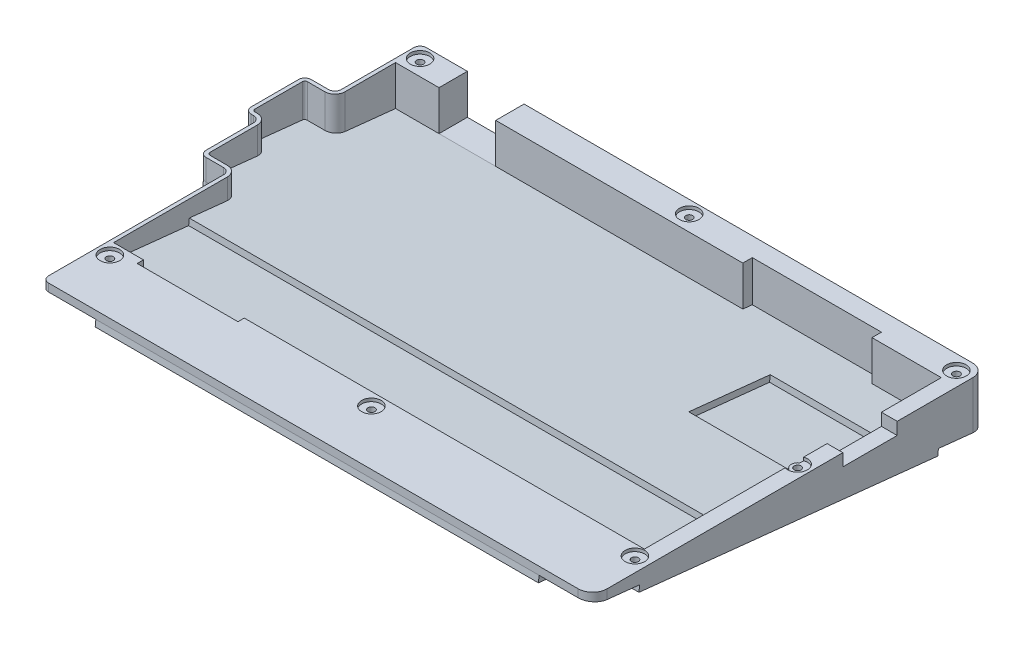
SolidWorks part; units mm, degrees
ref_plane "Front Plane" through (0, 0, 0) normal (0, 0, 1) x (1, 0, 0)
ref_plane "Top Plane" through (0, 0, 0) normal (0, 1, 0) x (1, 0, 0)
ref_plane "Right Plane" through (0, 0, 0) normal (1, 0, 0) x (0, 0, -1)
sketch "Sketch1" plane through (0, 0, 0) normal (0, 1, 0) x (1, 0, 0)
  line L0 (138.4196, 31.7518) -> (125.4196, 31.7518)
  line L1 (-35.0204, 31.7518) -> (107.4196, 31.7518)
  line L2 (140.4196, 29.7518) -> (140.4196, 6.7018)
  line L3 (-34.0204, 3.7518) -> (-34.0204, 22.7518)
  line L4 (136.4596, 27.7518) -> (136.4396, 27.7518)
  line L5 (142.4196, 4.7018) -> (147.9496, 4.7018)
  line L6 (-34.0204, 22.7518) -> (-12.0204, 22.7518)
  line L8 (149.9496, 2.7018) -> (149.9496, -12.3482)
  line L11 (147.9496, -14.3482) -> (147.1896, -14.3482)
  line L14 (145.1896, -16.3482) -> (145.1896, -31.3982)
  line L17 (143.1896, -33.3982) -> (137.6696, -33.3982)
  line L20 (135.6696, -35.3982) -> (135.6696, -77.4982)
  line L21 (-34.0204, -25.6003) -> (-34.0204, -71.4982)
  line L23 (133.6696, -79.4982) -> (-35.0204, -79.4982)
  line L28 (-39.0204, 27.7518) -> (-39.0204, 3.7518)
  line L31 (-34.0204, 3.7518) -> (-39.0204, 3.7518)
  line L32 (-34.0204, -13.4982) -> (-39.0204, -13.4982)
  line L33 (-39.0204, -75.4982) -> (-39.0204, -13.4982)
  line L34 (-34.0204, -71.4982) -> (92.9796, -71.4982)
  line L35 (92.9796, -71.4982) -> (92.9796, -73.4982)
  line L36 (92.9796, -73.4982) -> (124.9796, -73.4982)
  line L37 (124.9796, -73.4982) -> (124.9796, -71.4982)
  line L39 (134.4706, -35.3982) -> (134.4706, -71.4982)
  line L40 (134.4706, -71.4982) -> (124.9796, -71.4982)
  line L41 (137.6696, -32.1992) -> (143.1896, -32.1992)
  line L42 (-34.0204, -13.4982) -> (-34.0204, -22.1362)
  line L43 (143.9906, -31.3982) -> (143.9906, -16.3482)
  line L44 (-12.0204, 22.7518) -> (-12.0204, 25.7518)
  line L45 (147.1896, -13.1492) -> (147.9496, -13.1492)
  line L46 (148.7506, -12.3482) -> (148.7506, 2.7018)
  line L47 (-12.0204, 25.7518) -> (28.9796, 25.7518)
  line L48 (28.9796, 25.7518) -> (28.9796, 22.7518)
  line L49 (28.9796, 22.7518) -> (107.4196, 22.7518)
  line L50 (147.9496, 3.5027) -> (142.4196, 3.5027)
  line L51 (107.4196, 22.7518) -> (107.4196, 31.7518)
  line L52 (139.2206, 6.7018) -> (139.2206, 22.7518)
  line L53 (125.4196, 31.7518) -> (125.4196, 22.7518)
  line L54 (139.2206, 22.7518) -> (125.4196, 22.7518)
  arc A0 (138.4196, 31.7518) -> (140.4196, 29.7518) centre (138.4196, 29.7518) cw
  arc A1 (140.4196, 6.7018) -> (142.4196, 4.7018) centre (142.4196, 6.7018) ccw
  arc A2 (149.9496, 2.7018) -> (147.9496, 4.7018) centre (147.9496, 2.7018) ccw
  arc A3 (149.9496, -12.3482) -> (147.9496, -14.3482) centre (147.9496, -12.3482) cw
  arc A4 (147.1896, -14.3482) -> (145.1896, -16.3482) centre (147.1896, -16.3482) ccw
  arc A5 (145.1896, -31.3982) -> (143.1896, -33.3982) centre (143.1896, -31.3982) cw
  arc A6 (-35.0204, 31.7518) -> (-39.0204, 27.7518) centre (-35.0204, 27.7518) ccw
  arc A7 (-39.0204, -75.4982) -> (-35.0204, -79.4982) centre (-35.0204, -75.4982) ccw
  arc A8 (133.6696, -79.4982) -> (135.6696, -77.4982) centre (133.6696, -77.4982) ccw
  arc A9 (135.6696, -35.3982) -> (137.6696, -33.3982) centre (137.6696, -35.3982) cw
  circle A10 centre (-34.4204, 27.1518) radius 1.1
  circle A11 centre (51.0096, 27.7518) radius 1.1
  circle A12 centre (136.4396, 27.7518) radius 1.1
  circle A13 centre (-34.4204, -74.8982) radius 1.1
  circle A14 centre (48.6296, -75.4982) radius 1.1
  circle A15 centre (131.6496, -75.4982) radius 1.1
  circle A16 centre (-35.0204, -23.8682) radius 1.1
  arc A27 (-34.0204, -22.1362) -> (-34.0204, -25.6003) centre (-35.0204, -23.8682) cw
  arc A28 (139.2206, 6.7018) -> (142.4196, 3.5027) centre (142.4196, 6.7018) ccw
  arc A29 (147.9496, 3.5027) -> (148.7506, 2.7018) centre (147.9496, 2.7018) cw
  arc A30 (148.7506, -12.3482) -> (147.9496, -13.1492) centre (147.9496, -12.3482) cw
  arc A31 (147.1896, -13.1492) -> (143.9906, -16.3482) centre (147.1896, -16.3482) ccw
  arc A32 (143.9906, -31.3982) -> (143.1896, -32.1992) centre (143.1896, -31.3982) cw
  arc A33 (137.6696, -32.1992) -> (134.4706, -35.3982) centre (137.6696, -35.3982) ccw
extrude "Boss-Extrude2" add sketch "Sketch1" against normal blind 4.7 contours L41 A33 L39 L40 L37 L36 L35 L34 L21 A27 L42 L32 L33 A7 L23 A8 L20 A9 L17 A5 L14 A4 L11 A3 L8 A2 L5 A1 L2 A0 L0 L53 L54 L52 A28 L50 A29 L46 A30 L45 A31 L43 A32 A12 A13 A14 A15 | L1 A6 L28 L31 L3 L6 L44 L47 L48 L49 L51 A11 A10 region at (138.2833, 0, -29.6154) region at (31.7683, 0, -26.4895)
move or copy body "Body-Move/Copy1" bodies to move or copy 105 104 copy no rotation origin (55.4646, -2.35, 0) rotation axis (0, 0, 1) rotation angle 180
sketch "Sketch3" plane through (149.9496, 0, 0) normal (1, 0, 0) x (0, 0, -1)
  line L0 (-79.4982, 0) -> (-79.4982, -4.7) construction
  line L1 (-79.4982, 0) -> (-79.4982, -4.7)
  line L2 (31.7518, 0) -> (31.7518, -4.7) construction
  line L3 (31.7518, 0) -> (31.7518, -4.7)
  line L5 (-79.4982, -4.7) -> (31.7518, -16.3928)
  line L6 (31.7518, -16.3928) -> (31.7518, -4.7)
  line L7 (31.7518, -4.7) -> (-79.4982, -4.7)
  line M3 (-75.4982, -4.7) -> (-13.4982, -4.7)
  dimension "D1" = 6
extrude "Boss-Extrude3" add sketch "Sketch3" against normal up to surface (188.97 mm away) contours L6 L7 L5 M3 region at (149.9496, -8.5976, 5.3315) up to face at (-39.0204, -2.35, 4.8232)
sketch "Sketch4" plane through (0, -4.7, 0) normal (0, 1, 0) x (1, 0, 0)
  line L2 (145.9496, -79.4982) -> (149.9496, -79.4982)
  line L3 (149.9496, -79.4982) -> (149.9496, -75.4982)
  line L4 (-29.4904, 6.7018) -> (-29.4904, 29.7518)
  line L5 (-27.4904, 31.7518) -> (-39.0204, 31.7518)
  line L6 (-36.2604, -14.3482) -> (-37.0204, -14.3482)
  line L7 (-39.0204, -12.3482) -> (-39.0204, -79.4982)
  line L8 (-39.0204, -79.4982) -> (-22.7404, -79.4982)
  line L9 (-24.7404, -77.4982) -> (-24.7404, -35.3982)
  line L10 (-26.7404, -33.3982) -> (-32.2604, -33.3982)
  line L11 (-34.2604, -31.3982) -> (-34.2604, -16.3482)
  line L12 (-36.2604, -14.3482) -> (-37.0204, -14.3482)
  line L13 (-39.0204, -12.3482) -> (-39.0204, -79.4982)
  line L14 (-39.0204, -79.4982) -> (-22.7404, -79.4982)
  line L15 (-24.7404, -77.4982) -> (-24.7404, -35.3982)
  line L16 (-26.7404, -33.3982) -> (-32.2604, -33.3982)
  line L17 (-34.2604, -31.3982) -> (-34.2604, -16.3482)
  line L18 (-39.0204, 31.7518) -> (-39.0204, 2.7018)
  line L19 (-37.0204, 4.7018) -> (-31.4904, 4.7018)
  line L20 (-29.4904, 6.7018) -> (-29.4904, 29.7518)
  line L21 (-27.4904, 31.7518) -> (-39.0204, 31.7518)
  line L22 (-39.0204, 31.7518) -> (-39.0204, 2.7018)
  line L23 (-37.0204, 4.7018) -> (-31.4904, 4.7018)
  line L24 (145.9496, -79.4982) -> (149.9496, -79.4982)
  line L25 (149.9496, -79.4982) -> (149.9496, -75.4982)
  line L26 (149.9496, 31.7518) -> (145.9496, 31.7518)
  line L27 (149.9496, 27.7518) -> (149.9496, 31.7518)
  line L28 (149.9496, 31.7518) -> (145.9496, 31.7518)
  line L29 (149.9496, 27.7518) -> (149.9496, 31.7518)
  arc A1 (145.9496, -79.4982) -> (149.9496, -75.4982) centre (145.9496, -75.4982) ccw
  arc A2 (145.9496, -79.4982) -> (149.9496, -75.4982) centre (145.9496, -75.4982) ccw
  arc A3 (-27.4904, 31.7518) -> (-29.4904, 29.7518) centre (-27.4904, 29.7518) ccw
  arc A4 (-37.0204, 4.7018) -> (-39.0204, 2.7018) centre (-37.0204, 2.7018) ccw
  arc A5 (-39.0204, -12.3482) -> (-37.0204, -14.3482) centre (-37.0204, -12.3482) ccw
  arc A6 (-24.7404, -77.4982) -> (-22.7404, -79.4982) centre (-22.7404, -77.4982) ccw
  arc A7 (-24.7404, -35.3982) -> (-26.7404, -33.3982) centre (-26.7404, -35.3982) ccw
  arc A8 (-34.2604, -31.3982) -> (-32.2604, -33.3982) centre (-32.2604, -31.3982) ccw
  arc A9 (-34.2604, -16.3482) -> (-36.2604, -14.3482) centre (-36.2604, -16.3482) ccw
  arc A10 (-39.0204, -12.3482) -> (-37.0204, -14.3482) centre (-37.0204, -12.3482) ccw
  arc A11 (-24.7404, -77.4982) -> (-22.7404, -79.4982) centre (-22.7404, -77.4982) ccw
  arc A12 (-24.7404, -35.3982) -> (-26.7404, -33.3982) centre (-26.7404, -35.3982) ccw
  arc A13 (-34.2604, -31.3982) -> (-32.2604, -33.3982) centre (-32.2604, -31.3982) ccw
  arc A14 (-34.2604, -16.3482) -> (-36.2604, -14.3482) centre (-36.2604, -16.3482) ccw
  arc A15 (-31.4904, 4.7018) -> (-29.4904, 6.7018) centre (-31.4904, 6.7018) ccw
  arc A16 (-27.4904, 31.7518) -> (-29.4904, 29.7518) centre (-27.4904, 29.7518) ccw
  arc A17 (-37.0204, 4.7018) -> (-39.0204, 2.7018) centre (-37.0204, 2.7018) ccw
  arc A18 (-31.4904, 4.7018) -> (-29.4904, 6.7018) centre (-31.4904, 6.7018) ccw
  arc A19 (149.9496, 27.7518) -> (145.9496, 31.7518) centre (145.9496, 27.7518) ccw
  arc A20 (149.9496, 27.7518) -> (145.9496, 31.7518) centre (145.9496, 27.7518) ccw
  dimension "D1" = 0
  dimension "D2" = 0
  dimension "D3" = 0
  dimension "D4" = 0
extrude "Cut-Extrude1" cut sketch "Sketch4" against normal through all
ref_plane "Plane4" through (0, 15, 0) normal (0, 1, 0) x (1, 0, 0)
sketch "Sketch10" plane through (0, 15, 0) normal (0, 1, 0) x (1, 0, 0)
  line L0 (-14.4904, 22.7518) -> (3.5096, 22.7518)
  line L1 (144.9496, 3.7518) -> (144.9496, -13.4982)
  line L27 (-14.4904, 31.7518) -> (-14.4904, 22.7518)
  line L28 (-14.4904, 22.7518) -> (-28.2913, 22.7518)
  line L29 (-28.2913, 22.7518) -> (-28.2913, 6.7018)
  line L30 (-31.4904, 3.5027) -> (-37.0204, 3.5027)
  line L31 (-37.8213, 2.7018) -> (-37.8213, -12.3482)
  line L32 (-37.0204, -13.1492) -> (-36.2604, -13.1492)
  line L33 (-33.0613, -16.3482) -> (-33.0613, -31.3982)
  line L34 (-32.2604, -32.1992) -> (-26.7404, -32.1992)
  line L35 (-23.5413, -35.3982) -> (-23.5413, -71.4982)
  line L36 (-23.5413, -71.4982) -> (-14.0504, -71.4982)
  line L37 (-14.0504, -71.4982) -> (-14.0504, -73.4982)
  line L38 (-14.0504, -73.4982) -> (17.9496, -73.4982)
  line L39 (17.9496, -73.4982) -> (17.9496, -71.4982)
  line L40 (17.9496, -71.4982) -> (144.9496, -71.4982)
  line L41 (144.9496, -71.4982) -> (144.9496, -25.6003)
  line L42 (144.9496, -22.1362) -> (144.9496, -13.4982)
  line L43 (144.9496, -13.4982) -> (149.9496, -13.4982)
  line L44 (149.9496, -13.4982) -> (149.9496, 3.7518)
  line L45 (149.9496, 3.7518) -> (144.9496, 3.7518)
  line L46 (144.9496, 3.7518) -> (144.9496, 22.7518)
  line L47 (144.9496, 22.7518) -> (122.9496, 22.7518)
  line L48 (122.9496, 22.7518) -> (122.9496, 25.7518)
  line L49 (122.9496, 25.7518) -> (81.9496, 25.7518)
  line L50 (81.9496, 25.7518) -> (81.9496, 22.7518)
  line L51 (81.9496, 22.7518) -> (3.5096, 22.7518)
  line L52 (3.5096, 22.7518) -> (3.5096, 31.7518)
  line L53 (3.5096, 31.7518) -> (-14.4904, 31.7518)
  line L54 (-14.4904, 31.7518) -> (-14.4904, 22.7518)
  line L55 (-14.4904, 22.7518) -> (-28.2913, 22.7518)
  line L56 (-28.2913, 22.7518) -> (-28.2913, 6.7018)
  line L57 (-31.4904, 3.5027) -> (-37.0204, 3.5027)
  line L58 (-37.8213, 2.7018) -> (-37.8213, -12.3482)
  line L59 (-37.0204, -13.1492) -> (-36.2604, -13.1492)
  line L60 (-33.0613, -16.3482) -> (-33.0613, -31.3982)
  line L61 (-32.2604, -32.1992) -> (-26.7404, -32.1992)
  line L62 (-23.5413, -35.3982) -> (-23.5413, -71.4982)
  line L63 (-23.5413, -71.4982) -> (-14.0504, -71.4982)
  line L64 (-14.0504, -71.4982) -> (-14.0504, -73.4982)
  line L65 (-14.0504, -73.4982) -> (17.9496, -73.4982)
  line L66 (17.9496, -73.4982) -> (17.9496, -71.4982)
  line L67 (17.9496, -71.4982) -> (144.9496, -71.4982)
  line L68 (144.9496, -71.4982) -> (144.9496, -25.6003)
  line L69 (144.9496, -22.1362) -> (144.9496, -13.4982)
  line L70 (144.9496, -13.4982) -> (149.9496, -13.4982)
  line L71 (149.9496, -13.4982) -> (149.9496, 3.7518)
  line L72 (149.9496, 3.7518) -> (144.9496, 3.7518)
  line L73 (144.9496, 3.7518) -> (144.9496, 22.7518)
  line L74 (144.9496, 22.7518) -> (122.9496, 22.7518)
  line L75 (122.9496, 22.7518) -> (122.9496, 25.7518)
  line L76 (122.9496, 25.7518) -> (81.9496, 25.7518)
  line L77 (81.9496, 25.7518) -> (81.9496, 22.7518)
  line L78 (81.9496, 22.7518) -> (3.5096, 22.7518)
  line L79 (3.5096, 22.7518) -> (3.5096, 31.7518)
  line L80 (3.5096, 31.7518) -> (-14.4904, 31.7518)
  arc A7 (-31.4904, 3.5027) -> (-28.2913, 6.7018) centre (-31.4904, 6.7018) ccw
  arc A8 (-37.0204, 3.5027) -> (-37.8213, 2.7018) centre (-37.0204, 2.7018) ccw
  arc A9 (-37.8213, -12.3482) -> (-37.0204, -13.1492) centre (-37.0204, -12.3482) ccw
  arc A10 (-33.0613, -16.3482) -> (-36.2604, -13.1492) centre (-36.2604, -16.3482) ccw
  arc A11 (-33.0613, -31.3982) -> (-32.2604, -32.1992) centre (-32.2604, -31.3982) ccw
  arc A12 (-23.5413, -35.3982) -> (-26.7404, -32.1992) centre (-26.7404, -35.3982) ccw
  arc A13 (144.9496, -22.1362) -> (144.9496, -25.6003) centre (145.9496, -23.8682) ccw
  arc A14 (-31.4904, 3.5027) -> (-28.2913, 6.7018) centre (-31.4904, 6.7018) ccw
  arc A15 (-37.0204, 3.5027) -> (-37.8213, 2.7018) centre (-37.0204, 2.7018) ccw
  arc A16 (-37.8213, -12.3482) -> (-37.0204, -13.1492) centre (-37.0204, -12.3482) ccw
  arc A17 (-33.0613, -16.3482) -> (-36.2604, -13.1492) centre (-36.2604, -16.3482) ccw
  arc A18 (-33.0613, -31.3982) -> (-32.2604, -32.1992) centre (-32.2604, -31.3982) ccw
  arc A19 (-23.5413, -35.3982) -> (-26.7404, -32.1992) centre (-26.7404, -35.3982) ccw
  arc A20 (144.9496, -22.1362) -> (144.9496, -25.6003) centre (145.9496, -23.8682) ccw
  dimension "D1" = 0
extrude "Cut-Extrude2" cut sketch "Sketch10" against normal through all contours A20 L69 L1 L73 L74 L75 L76 L77 L78 L0 L55 L56 A14 L57 A15 L58 A16 L59 A17 L60 A18 L61 A19 L62 L63 L64 L65 L66 L67 L68 region at (57.9798, 15, 23.6888)
sketch "Sketch11" plane through (144.9496, 0, 0) normal (-1, 0, 0) x (0, 0, 1)
  line L0 (-22.7518, -15.4469) -> (71.4982, -5.5408)
  line L1 (71.4982, -5.5408) -> (71.4982, -3.5408)
  line L2 (71.4982, 0) -> (71.4982, -5.5408) construction
  line L3 (71.4982, -3.5408) -> (-22.7518, -13.4469)
  line L4 (-22.7518, 0) -> (-22.7518, -15.4469) construction
  line L5 (-22.7518, -13.4469) -> (-22.7518, -15.4469)
  dimension "D1" = 2
  dimension "D2" = 2
extrude "Boss-Extrude4" add sketch "Sketch11" along normal up to surface (182.7709 mm away)
sketch "Sketch12" plane through (0, -10.9348, 1.1493) normal (0, 0.9945, -0.1045) x (1, 0, 0)
  line L0 (-29.4904, 7.8943) -> (-29.4904, 24.0327) construction
  line L1 (-29.4904, 24.0327) -> (-37.8213, 24.0327) construction
  line L2 (-37.8213, 24.0327) -> (-37.8213, 5.715) construction
  line L3 (-37.0204, 5.8833) -> (-31.4904, 5.8833) construction
  line L4 (-36.2604, -13.2716) -> (-37.0204, -13.2716) construction
  line L5 (-37.8213, -13.1033) -> (-37.8213, -70.7364) construction
  line L6 (-37.8213, -70.7364) -> (-24.7404, -70.7364) construction
  line L7 (-24.7404, -70.7364) -> (-24.7404, -34.4376) construction
  line L8 (-26.7404, -32.4266) -> (-32.2604, -32.4266) construction
  line L9 (-34.2604, -30.4155) -> (-34.2604, -15.2826) construction
  line L10 (-29.4904, 7.8943) -> (-29.4904, 24.0327)
  line L11 (-29.4904, 24.0327) -> (-37.8213, 24.0327)
  line L12 (-37.8213, 24.0327) -> (-37.8213, 5.715)
  line L13 (-37.0204, 5.8833) -> (-31.4904, 5.8833)
  line L14 (-36.2604, -13.2716) -> (-37.0204, -13.2716)
  line L15 (-37.8213, -13.1033) -> (-37.8213, -70.7364)
  line L16 (-37.8213, -70.7364) -> (-24.7404, -70.7364)
  line L17 (-24.7404, -70.7364) -> (-24.7404, -34.4376)
  line L18 (-26.7404, -32.4266) -> (-32.2604, -32.4266)
  line L19 (-34.2604, -30.4155) -> (-34.2604, -15.2826)
  line L20 (-37.8213, 24.0327) -> (-37.8213, 25.9101)
  line L21 (-29.4904, 24.0327) -> (-29.4904, 27.1127)
  line L22 (-29.4904, 27.1127) -> (-37.8213, 25.9101)
  ellipse E0 centre (-31.4904, 7.8943) end of major axis (-31.4904, 9.9053) minor radius 2 (-31.4904, 5.8833) -> (-29.4904, 7.8943) ccw construction
  ellipse E1 centre (-37.0204, 3.8723) end of major axis (-37.0204, 5.8833) minor radius 2 (-37.0204, 5.8833) -> (-37.8213, 5.715) ccw construction
  ellipse E2 centre (-37.0204, -11.2606) end of major axis (-37.0204, -9.2496) minor radius 2 (-37.8213, -13.1033) -> (-37.0204, -13.2716) ccw construction
  ellipse E3 centre (-26.7404, -34.4376) end of major axis (-26.7404, -32.4266) minor radius 2 (-24.7404, -34.4376) -> (-26.7404, -32.4266) ccw construction
  ellipse E4 centre (-32.2604, -30.4155) end of major axis (-32.2604, -28.4045) minor radius 2 (-34.2604, -30.4155) -> (-32.2604, -32.4266) ccw construction
  ellipse E5 centre (-36.2604, -15.2826) end of major axis (-36.2604, -13.2716) minor radius 2 (-34.2604, -15.2826) -> (-36.2604, -13.2716) ccw construction
  ellipse E6 centre (-31.4904, 7.8943) end of major axis (-31.4904, 9.9053) minor radius 2 (-31.4904, 5.8833) -> (-29.4904, 7.8943) ccw
  ellipse E7 centre (-37.0204, 3.8723) end of major axis (-37.0204, 5.8833) minor radius 2 (-37.0204, 5.8833) -> (-37.8213, 5.715) ccw
  ellipse E8 centre (-37.0204, -11.2606) end of major axis (-37.0204, -9.2496) minor radius 2 (-37.8213, -13.1033) -> (-37.0204, -13.2716) ccw
  ellipse E9 centre (-26.7404, -34.4376) end of major axis (-26.7404, -32.4266) minor radius 2 (-24.7404, -34.4376) -> (-26.7404, -32.4266) ccw
  ellipse E10 centre (-32.2604, -30.4155) end of major axis (-32.2604, -28.4045) minor radius 2 (-34.2604, -30.4155) -> (-32.2604, -32.4266) ccw
  ellipse E11 centre (-36.2604, -15.2826) end of major axis (-36.2604, -13.2716) minor radius 2 (-34.2604, -15.2826) -> (-36.2604, -13.2716) ccw
sketch "Sketch26" plane through (-37.8213, 0, 0) normal (-1, 0, 0) x (0, 0, 1)
  line L0 (14.1808, -9.5651) -> (-4.5344, -11.5322)
  line L1 (-4.5344, -13.5322) -> (14.1808, -11.5651)
  line L4 (-22.7518, -15.4469) -> (-4.5344, -13.5322)
  line L5 (-4.5344, -13.5322) -> (-4.5344, -11.5322)
  line L6 (-4.5344, -11.5322) -> (-22.7518, -13.4469)
  line L7 (-22.7518, -13.4469) -> (-22.7518, -15.4469)
  line L8 (-22.7518, -15.4469) -> (-4.5344, -13.5322)
  line L9 (-4.5344, -13.5322) -> (-4.5344, -11.5322)
  line L10 (-4.5344, -11.5322) -> (-22.7518, -13.4469)
  line L11 (-22.7518, -13.4469) -> (-22.7518, -15.4469)
  line L12 (14.1808, -9.5651) -> (14.1808, -11.5651)
  line L13 (14.1808, -11.5651) -> (71.4982, -5.5408)
  line L14 (71.4982, -5.5408) -> (71.4982, -3.5408)
  line L15 (71.4982, -3.5408) -> (14.1808, -9.5651)
  line L16 (14.1808, -9.5651) -> (14.1808, -11.5651)
  line L17 (14.1808, -11.5651) -> (71.4982, -5.5408)
  line L18 (71.4982, -5.5408) -> (71.4982, -3.5408)
  line L19 (71.4982, -3.5408) -> (14.1808, -9.5651)
  line M9 (14.1808, -9.5651) -> (14.1808, -11.5651)
  line M10 (14.1808, -11.5651) -> (71.4982, -5.5408)
  line M11 (71.4982, -5.5408) -> (71.4982, -3.5408)
  line M12 (71.4982, -3.5408) -> (14.1808, -9.5651)
  dimension "D1" = 0
  dimension "D2" = 0
extrude "Boss-Extrude10" add sketch "Sketch26" along normal blind 11 contours L10 L11 L8 L9 | L9 L1 L0 M9 | M12 M9 M10 M11 region at (-37.8213, -11.5487, 4.8232) region at (-37.8213, -7.553, 42.8395) region at (-37.8213, -13.4895, -13.6431)
sketch "Sketch28" plane through (0, -10.9348, 1.1493) normal (0, 0.9945, -0.1045) x (1, 0, 0)
  line L0 (-48.8213, 24.0327) -> (-52.7132, 28.3929)
  line L1 (-52.7132, 28.3929) -> (-29.4904, 30.8021)
  line L2 (-29.4904, 30.8021) -> (-29.4904, 24.0327)
  line L10 (-29.4904, 7.8943) -> (-29.4904, 24.0327)
  line L11 (-29.4904, 24.0327) -> (-48.8213, 24.0327)
  line L12 (-48.8213, 24.0327) -> (-48.8213, -70.7364)
  line L13 (-48.8213, -70.7364) -> (-24.7404, -70.7364)
  line L14 (-24.7404, -70.7364) -> (-24.7404, -34.4376)
  line L15 (-26.7404, -32.4266) -> (-32.2604, -32.4266)
  line L16 (-34.2604, -30.4155) -> (-34.2604, -15.2826)
  line L17 (-36.2604, -13.2716) -> (-37.0204, -13.2716)
  line L18 (-39.0204, -11.2606) -> (-39.0204, 3.8723)
  line L19 (-37.0204, 5.8833) -> (-31.4904, 5.8833)
  line L20 (-29.4904, 7.8943) -> (-29.4904, 24.0327)
  line L21 (-29.4904, 24.0327) -> (-48.8213, 24.0327)
  line L22 (-48.8213, 24.0327) -> (-48.8213, -70.7364)
  line L23 (-48.8213, -70.7364) -> (-24.7404, -70.7364)
  line L24 (-24.7404, -70.7364) -> (-24.7404, -34.4376)
  line L25 (-26.7404, -32.4266) -> (-32.2604, -32.4266)
  line L26 (-34.2604, -30.4155) -> (-34.2604, -15.2826)
  line L27 (-36.2604, -13.2716) -> (-37.0204, -13.2716)
  line L28 (-39.0204, -11.2606) -> (-39.0204, 3.8723)
  line L29 (-37.0204, 5.8833) -> (-31.4904, 5.8833)
  ellipse E6 centre (-31.4904, 7.8943) end of major axis (-31.4904, 9.9053) minor radius 2 (-31.4904, 5.8833) -> (-29.4904, 7.8943) ccw
  ellipse E7 centre (-26.7404, -34.4376) end of major axis (-26.7404, -32.4266) minor radius 2 (-24.7404, -34.4376) -> (-26.7404, -32.4266) ccw
  ellipse E8 centre (-32.2604, -30.4155) end of major axis (-32.2604, -28.4045) minor radius 2 (-34.2604, -30.4155) -> (-32.2604, -32.4266) ccw
  ellipse E9 centre (-36.2604, -15.2826) end of major axis (-36.2604, -13.2716) minor radius 2 (-34.2604, -15.2826) -> (-36.2604, -13.2716) ccw
  ellipse E10 centre (-37.0204, -11.2606) end of major axis (-37.0204, -9.2496) minor radius 2 (-39.0204, -11.2606) -> (-37.0204, -13.2716) ccw
  ellipse E11 centre (-37.0204, 3.8723) end of major axis (-37.0204, 5.8833) minor radius 2 (-37.0204, 5.8833) -> (-39.0204, 3.8723) ccw
  ellipse E12 centre (-31.4904, 7.8943) end of major axis (-31.4904, 9.9053) minor radius 2 (-31.4904, 5.8833) -> (-29.4904, 7.8943) ccw
  ellipse E13 centre (-26.7404, -34.4376) end of major axis (-26.7404, -32.4266) minor radius 2 (-24.7404, -34.4376) -> (-26.7404, -32.4266) ccw
  ellipse E14 centre (-32.2604, -30.4155) end of major axis (-32.2604, -28.4045) minor radius 2 (-34.2604, -30.4155) -> (-32.2604, -32.4266) ccw
  ellipse E15 centre (-36.2604, -15.2826) end of major axis (-36.2604, -13.2716) minor radius 2 (-34.2604, -15.2826) -> (-36.2604, -13.2716) ccw
  ellipse E16 centre (-37.0204, -11.2606) end of major axis (-37.0204, -9.2496) minor radius 2 (-39.0204, -11.2606) -> (-37.0204, -13.2716) ccw
  ellipse E17 centre (-37.0204, 3.8723) end of major axis (-37.0204, 5.8833) minor radius 2 (-37.0204, 5.8833) -> (-39.0204, 3.8723) ccw
  ellipse M17 centre (-31.4904, 7.8943) end of major axis (-31.4904, 9.9053) minor radius 2 (-31.4904, 5.8833) -> (-29.4904, 7.8943) ccw
  line M18 (-29.4904, 7.8943) -> (-29.4904, 24.0327)
  line M19 (-29.4904, 24.0327) -> (-48.8213, 24.0327)
  line M20 (-48.8213, 24.0327) -> (-48.8213, -70.7364)
  line M21 (-48.8213, -70.7364) -> (-24.7404, -70.7364)
  line M22 (-24.7404, -70.7364) -> (-24.7404, -34.4376)
  ellipse M23 centre (-26.7404, -34.4376) end of major axis (-26.7404, -32.4266) minor radius 2 (-24.7404, -34.4376) -> (-26.7404, -32.4266) ccw
  line M24 (-26.7404, -32.4266) -> (-32.2604, -32.4266)
  ellipse M25 centre (-32.2604, -30.4155) end of major axis (-32.2604, -28.4045) minor radius 2 (-32.2604, -32.4266) -> (-34.2604, -30.4155) cw
  line M26 (-34.2604, -30.4155) -> (-34.2604, -15.2826)
  ellipse M27 centre (-36.2604, -15.2826) end of major axis (-36.2604, -13.2716) minor radius 2 (-34.2604, -15.2826) -> (-36.2604, -13.2716) ccw
  line M28 (-36.2604, -13.2716) -> (-37.0204, -13.2716)
  ellipse M29 centre (-37.0204, -11.2606) end of major axis (-37.0204, -9.2496) minor radius 2 (-37.0204, -13.2716) -> (-39.0204, -11.2606) cw
  line M30 (-39.0204, -11.2606) -> (-39.0204, 3.8723)
  ellipse M31 centre (-37.0204, 3.8723) end of major axis (-37.0204, 5.8833) minor radius 2 (-39.0204, 3.8723) -> (-37.0204, 5.8833) cw
  line M32 (-37.0204, 5.8833) -> (-31.4904, 5.8833)
  dimension "D1" = 0
extrude "Cut-Extrude8" cut sketch "Sketch28" against normal blind 11 contours M32 M17 M18 M19 M20 M21 M22 M23 M24 M25 M26 M27 M28 M29 M30 M31 | L2 L1 L0 M19 region at (-39.4803, -13.7524, -25.6581) region at (-38.8035, -7.967, 29.3861)
sketch "Sketch30" plane through (122.9496, 0, 0) normal (-1, 0, 0) x (0, 0, 1)
  line L0 (-25.7518, -15.7622) -> (-22.7518, -15.4469)
  line L1 (-22.7518, -15.4469) -> (-22.7518, -13.4469)
  line L2 (-22.7518, -15.4469) -> (-22.7518, -13.4469) construction
  line L3 (-22.7518, -13.4469) -> (-25.7518, -13.7622)
  line L4 (-25.7518, 0) -> (-25.7518, -15.7622) construction
  line L5 (-25.7518, -13.7622) -> (-25.7518, -15.7622)
extrude "Boss-Extrude11" add sketch "Sketch30" along normal up to surface (41 mm away)
sketch "Sketch32" plane through (17.9496, 0, 0) normal (-1, 0, 0) x (0, 0, 1)
  line L0 (73.4982, -5.3306) -> (71.4982, -5.5408)
  line L1 (71.4982, -5.5408) -> (71.4982, -3.5408)
  line L2 (71.4982, -3.5408) -> (73.4982, -3.3306)
  line L3 (73.4982, 0) -> (73.4982, -5.3306) construction
  line L4 (73.4982, -3.3306) -> (73.4982, -5.3306)
  dimension "D1" = 2
extrude "Boss-Extrude14" add sketch "Sketch32" along normal up to surface (32 mm away)
sketch "Sketch35" plane through (0, 0, 0) normal (0, 1, 0) x (1, 0, 0)
  line L0 (149.9496, 3.7518) -> (149.9496, -13.4982)
  line L1 (149.9496, -13.4982) -> (144.9496, -13.4982)
  line L2 (144.9496, -13.4982) -> (144.9496, 3.7518)
  line L3 (144.9496, 3.7518) -> (149.9496, 3.7518)
ref_plane "Plane5" through (149.9496, -5.1204, 75.4982) normal (0, -1, 0) x (-1, 0, 0)
sketch "Sketch47" plane through (0, 0, 0) normal (0, 1, 0) x (1, 0, 0)
  circle A0 centre (145.3496, -74.8982) radius 3.1
  circle A1 centre (62.2996, -75.4982) radius 3.1
  circle A2 centre (-20.7204, -75.4982) radius 3.1
  circle A3 centre (-25.5104, 27.7518) radius 3.1
  circle A4 centre (59.9196, 27.7518) radius 3.1
  circle A5 centre (145.3496, 27.1518) radius 3.1
  circle A6 centre (145.9496, -23.8682) radius 3.1
extrude "Cut-Extrude17" cut sketch "Sketch47" against normal blind 1.8
sketch "Sketch48" plane through (0, 0, 0) normal (0, 1, 0) x (1, 0, 0)
  line L10 (145.9496, 31.7518) -> (3.5096, 31.7518)
  line L11 (3.5096, 31.7518) -> (3.5096, 22.7518)
  line L12 (3.5096, 22.7518) -> (81.9496, 22.7518)
  line L13 (81.9496, 22.7518) -> (81.9496, 25.7518)
  line L14 (81.9496, 25.7518) -> (122.9496, 25.7518)
  line L15 (122.9496, 25.7518) -> (122.9496, 22.7518)
  line L16 (122.9496, 22.7518) -> (144.9496, 22.7518)
  line L17 (144.9496, 22.7518) -> (144.9496, 3.7518)
  line L18 (144.9496, 3.7518) -> (149.9496, 3.7518)
  line L19 (149.9496, 3.7518) -> (149.9496, 27.7518)
  line L20 (145.9496, 31.7518) -> (3.5096, 31.7518)
  line L21 (3.5096, 31.7518) -> (3.5096, 22.7518)
  line L22 (3.5096, 22.7518) -> (81.9496, 22.7518)
  line L23 (81.9496, 22.7518) -> (81.9496, 25.7518)
  line L24 (81.9496, 25.7518) -> (122.9496, 25.7518)
  line L25 (122.9496, 25.7518) -> (122.9496, 22.7518)
  line L26 (122.9496, 22.7518) -> (144.9496, 22.7518)
  line L27 (144.9496, 22.7518) -> (144.9496, 3.7518)
  line L28 (144.9496, 3.7518) -> (149.9496, 3.7518)
  line L29 (149.9496, 3.7518) -> (149.9496, 27.7518)
  line L47 (144.9496, -13.4982) -> (144.9496, -20.9339)
  line L48 (144.9496, -26.8025) -> (144.9496, -71.4982)
  line L49 (144.9496, -71.4982) -> (17.9496, -71.4982)
  line L50 (17.9496, -71.4982) -> (17.9496, -73.4982)
  line L51 (17.9496, -73.4982) -> (-14.0504, -73.4982)
  line L52 (-14.0504, -73.4982) -> (-14.0504, -71.4982)
  line L53 (-14.0504, -71.4982) -> (-23.5413, -71.4982)
  line L54 (-23.5413, -71.4982) -> (-23.5413, -35.3982)
  line L55 (-26.7404, -32.1992) -> (-32.2604, -32.1992)
  line L56 (-33.0613, -31.3982) -> (-33.0613, -16.3482)
  line L57 (-36.2604, -13.1492) -> (-37.0204, -13.1492)
  line L58 (-37.8213, -12.3482) -> (-37.8213, 2.7018)
  line L59 (-37.0204, 3.5027) -> (-31.4904, 3.5027)
  line L60 (-28.2913, 6.7018) -> (-28.2913, 22.7518)
  line L61 (-28.2913, 22.7518) -> (-14.4904, 22.7518)
  line L62 (-14.4904, 22.7518) -> (-14.4904, 31.7518)
  line L63 (-14.4904, 31.7518) -> (-27.4904, 31.7518)
  line L64 (-29.4904, 29.7518) -> (-29.4904, 6.7018)
  line L65 (-31.4904, 4.7018) -> (-37.0204, 4.7018)
  line L66 (-39.0204, 2.7018) -> (-39.0204, -12.3482)
  line L67 (-37.0204, -14.3482) -> (-36.2604, -14.3482)
  line L68 (-34.2604, -16.3482) -> (-34.2604, -31.3982)
  line L69 (-32.2604, -33.3982) -> (-26.7404, -33.3982)
  line L70 (-24.7404, -35.3982) -> (-24.7404, -77.4982)
  line L71 (-22.7404, -79.4982) -> (145.9496, -79.4982)
  line L72 (149.9496, -75.4982) -> (149.9496, -13.4982)
  line L73 (149.9496, -13.4982) -> (144.9496, -13.4982)
  line L74 (144.9496, -13.4982) -> (144.9496, -20.9339)
  line L75 (144.9496, -26.8025) -> (144.9496, -71.4982)
  line L76 (144.9496, -71.4982) -> (17.9496, -71.4982)
  line L77 (17.9496, -71.4982) -> (17.9496, -73.4982)
  line L78 (17.9496, -73.4982) -> (-14.0504, -73.4982)
  line L79 (-14.0504, -73.4982) -> (-14.0504, -71.4982)
  line L80 (-14.0504, -71.4982) -> (-23.5413, -71.4982)
  line L81 (-23.5413, -71.4982) -> (-23.5413, -35.3982)
  line L82 (-26.7404, -32.1992) -> (-32.2604, -32.1992)
  line L83 (-33.0613, -31.3982) -> (-33.0613, -16.3482)
  line L84 (-36.2604, -13.1492) -> (-37.0204, -13.1492)
  line L85 (-37.8213, -12.3482) -> (-37.8213, 2.7018)
  line L86 (-37.0204, 3.5027) -> (-31.4904, 3.5027)
  line L87 (-28.2913, 6.7018) -> (-28.2913, 22.7518)
  line L88 (-28.2913, 22.7518) -> (-14.4904, 22.7518)
  line L89 (-14.4904, 22.7518) -> (-14.4904, 31.7518)
  line L90 (-14.4904, 31.7518) -> (-27.4904, 31.7518)
  line L91 (-29.4904, 29.7518) -> (-29.4904, 6.7018)
  line L92 (-31.4904, 4.7018) -> (-37.0204, 4.7018)
  line L93 (-39.0204, 2.7018) -> (-39.0204, -12.3482)
  line L94 (-37.0204, -14.3482) -> (-36.2604, -14.3482)
  line L95 (-34.2604, -16.3482) -> (-34.2604, -31.3982)
  line L96 (-32.2604, -33.3982) -> (-26.7404, -33.3982)
  line L97 (-24.7404, -35.3982) -> (-24.7404, -77.4982)
  line L98 (-22.7404, -79.4982) -> (145.9496, -79.4982)
  line L99 (149.9496, -75.4982) -> (149.9496, -13.4982)
  line L100 (149.9496, -13.4982) -> (144.9496, -13.4982)
  arc A1 (149.9496, 27.7518) -> (145.9496, 31.7518) centre (145.9496, 27.7518) ccw
  arc A2 (149.9496, 27.7518) -> (145.9496, 31.7518) centre (145.9496, 27.7518) ccw
  arc A18 (144.9496, -26.8025) -> (144.9496, -20.9339) centre (145.9496, -23.8682) ccw
  arc A19 (-23.5413, -35.3982) -> (-26.7404, -32.1992) centre (-26.7404, -35.3982) ccw
  arc A20 (-33.0613, -31.3982) -> (-32.2604, -32.1992) centre (-32.2604, -31.3982) ccw
  arc A21 (-33.0613, -16.3482) -> (-36.2604, -13.1492) centre (-36.2604, -16.3482) ccw
  arc A22 (-37.8213, -12.3482) -> (-37.0204, -13.1492) centre (-37.0204, -12.3482) ccw
  arc A23 (-37.0204, 3.5027) -> (-37.8213, 2.7018) centre (-37.0204, 2.7018) ccw
  arc A24 (-31.4904, 3.5027) -> (-28.2913, 6.7018) centre (-31.4904, 6.7018) ccw
  arc A25 (-27.4904, 31.7518) -> (-29.4904, 29.7518) centre (-27.4904, 29.7518) ccw
  arc A26 (-31.4904, 4.7018) -> (-29.4904, 6.7018) centre (-31.4904, 6.7018) ccw
  arc A27 (-37.0204, 4.7018) -> (-39.0204, 2.7018) centre (-37.0204, 2.7018) ccw
  arc A28 (-39.0204, -12.3482) -> (-37.0204, -14.3482) centre (-37.0204, -12.3482) ccw
  arc A29 (-34.2604, -16.3482) -> (-36.2604, -14.3482) centre (-36.2604, -16.3482) ccw
  arc A30 (-34.2604, -31.3982) -> (-32.2604, -33.3982) centre (-32.2604, -31.3982) ccw
  arc A31 (-24.7404, -35.3982) -> (-26.7404, -33.3982) centre (-26.7404, -35.3982) ccw
  arc A32 (-24.7404, -77.4982) -> (-22.7404, -79.4982) centre (-22.7404, -77.4982) ccw
  arc A33 (145.9496, -79.4982) -> (149.9496, -75.4982) centre (145.9496, -75.4982) ccw
  arc A34 (144.9496, -26.8025) -> (144.9496, -20.9339) centre (145.9496, -23.8682) ccw
  arc A35 (-23.5413, -35.3982) -> (-26.7404, -32.1992) centre (-26.7404, -35.3982) ccw
  arc A36 (-33.0613, -31.3982) -> (-32.2604, -32.1992) centre (-32.2604, -31.3982) ccw
  arc A37 (-33.0613, -16.3482) -> (-36.2604, -13.1492) centre (-36.2604, -16.3482) ccw
  arc A38 (-37.8213, -12.3482) -> (-37.0204, -13.1492) centre (-37.0204, -12.3482) ccw
  arc A39 (-37.0204, 3.5027) -> (-37.8213, 2.7018) centre (-37.0204, 2.7018) ccw
  arc A40 (-31.4904, 3.5027) -> (-28.2913, 6.7018) centre (-31.4904, 6.7018) ccw
  arc A41 (-27.4904, 31.7518) -> (-29.4904, 29.7518) centre (-27.4904, 29.7518) ccw
  arc A42 (-31.4904, 4.7018) -> (-29.4904, 6.7018) centre (-31.4904, 6.7018) ccw
  arc A43 (-37.0204, 4.7018) -> (-39.0204, 2.7018) centre (-37.0204, 2.7018) ccw
  arc A44 (-39.0204, -12.3482) -> (-37.0204, -14.3482) centre (-37.0204, -12.3482) ccw
  arc A45 (-34.2604, -16.3482) -> (-36.2604, -14.3482) centre (-36.2604, -16.3482) ccw
  arc A46 (-34.2604, -31.3982) -> (-32.2604, -33.3982) centre (-32.2604, -31.3982) ccw
  arc A47 (-24.7404, -35.3982) -> (-26.7404, -33.3982) centre (-26.7404, -35.3982) ccw
  arc A48 (-24.7404, -77.4982) -> (-22.7404, -79.4982) centre (-22.7404, -77.4982) ccw
  arc A49 (145.9496, -79.4982) -> (149.9496, -75.4982) centre (145.9496, -75.4982) ccw
  dimension "D1" = 0
  dimension "D2" = 0
extrude "Cut-Extrude18" cut sketch "Sketch48" against normal blind 0.8
sketch "Sketch49" plane through (0, -12.913, 1.3572) normal (0, -0.9945, 0.1045) x (1, 0, 0)
  line L0 (17.9496, 70.7364) -> (144.9496, 70.7364) construction
  line L1 (17.9496, 70.7364) -> (144.9496, 70.7364)
  line L2 (-23.5413, 46.5714) -> (-23.5413, 70.7364)
  line L6 (144.9496, 46.5714) -> (144.9496, 70.7364)
  line L9 (17.9496, 70.7364) -> (-23.5413, 70.7364)
  line L10 (144.9496, 46.5714) -> (-23.5413, 46.5714)
extrude "Cut-Extrude19" cut sketch "Sketch49" against normal blind 10
sketch "Sketch50" plane through (0, -12.913, 1.3572) normal (0, -0.9945, 0.1045) x (1, 0, 0)
  line L5 (105.9496, 17.3552) -> (105.9496, -8.6448)
  line L7 (144.9496, -8.6448) -> (144.9496, 17.3552)
  line L12 (105.9496, -8.6448) -> (144.9496, -8.6448)
  line L13 (105.9496, 17.3552) -> (144.9496, 17.3552)
extrude "Cut-Extrude20" cut sketch "Sketch50" against normal blind 10
sketch "Sketch51" plane through (0, 0, 79.4982) normal (0, 0, 1) x (1, 0, 0)
  line L4 (145.9496, -0.8) -> (-22.7404, -0.8)
  line L5 (-22.7404, -0.8) -> (-22.7404, -4.7)
  line L6 (-22.7404, -4.7) -> (145.9496, -4.7)
  line L7 (145.9496, -4.7) -> (145.9496, -0.8)
  line L8 (145.9496, -0.8) -> (-22.7404, -0.8)
  line L9 (-22.7404, -0.8) -> (-22.7404, -4.7)
  line L10 (-22.7404, -4.7) -> (145.9496, -4.7)
  line L11 (145.9496, -4.7) -> (145.9496, -0.8)
  dimension "D1" = 0
extrude "Boss-Extrude15" add sketch "Sketch51" along normal blind 13.5
sketch "Sketch52" plane through (0, 0, 92.9982) normal (0, 0, 1) x (1, 0, 0)
  line L4 (145.9496, -4.7) -> (145.9496, -0.8)
  line L5 (145.9496, -0.8) -> (-22.7404, -0.8)
  line L6 (-22.7404, -0.8) -> (-22.7404, -4.7)
  line L7 (-22.7404, -4.7) -> (145.9496, -4.7)
  line L8 (145.9496, -4.7) -> (145.9496, -0.8)
  line L9 (145.9496, -0.8) -> (-22.7404, -0.8)
  line L10 (-22.7404, -0.8) -> (-22.7404, -4.7)
  line L11 (-22.7404, -4.7) -> (145.9496, -4.7)
  dimension "D1" = 0
extrude "Cut-Extrude21" cut sketch "Sketch52" against normal blind 13.5
sketch "Sketch53" plane through (149.9496, 0, 0) normal (1, 0, 0) x (0, 0, -1)
  line L0 (-79.4982, -4.7) -> (-92.9243, -3.2889)
  line L1 (-79.4982, -0.8) -> (-92.9243, -0.8)
  line L2 (-92.9243, -0.8) -> (-92.9243, -3.2889)
  line L4 (-75.4982, -5.1204) -> (-75.4982, -0.8)
  line L5 (-75.4982, -0.8) -> (-79.4982, -0.8)
  line L6 (-79.4982, -0.8) -> (-79.4982, -4.7)
  line L7 (-79.4982, -4.7) -> (-75.4982, -5.1204)
  line L8 (-75.4982, -5.1204) -> (-75.4982, -0.8)
  line L9 (-75.4982, -0.8) -> (-79.4982, -0.8)
  line L10 (-79.4982, -0.8) -> (-79.4982, -4.7)
  line L11 (-79.4982, -4.7) -> (-75.4982, -5.1204)
  dimension "D1" = 0
extrude "Boss-Extrude16" add sketch "Sketch53" against normal up to surface (174.69 mm away) contours L10 L1 L2 L0 region at (149.9496, -2.4232, 85.717) up to face at (-24.7404, -4.6317, 52.2798)
sketch "Sketch54" plane through (0, 0, 79.4982) normal (0, 0, -1) x (-1, 0, 0)
  line L0 (22.7404, -4.7) -> (22.7404, -6.6661)
  line L1 (22.7404, -6.6661) -> (24.7404, -6.6661)
  line L2 (24.7404, -6.6661) -> (24.7404, -4.7)
  line L4 (22.7404, -0.8) -> (22.7404, -4.7)
  line L5 (22.7404, -4.7) -> (24.7404, -4.7)
  line L6 (24.7404, -4.7) -> (24.7404, -0.8)
  line L7 (24.7404, -0.8) -> (22.7404, -0.8)
  line L8 (22.7404, -0.8) -> (22.7404, -4.7)
  line L9 (22.7404, -4.7) -> (24.7404, -4.7)
  line L10 (24.7404, -4.7) -> (24.7404, -0.8)
  line L11 (24.7404, -0.8) -> (22.7404, -0.8)
  line M5 (22.7404, -0.8) -> (22.7404, -4.7)
  line M6 (22.7404, -4.7) -> (24.7404, -4.7)
  line M7 (24.7404, -4.7) -> (24.7404, -0.8)
  line M8 (24.7404, -0.8) -> (22.7404, -0.8)
  dimension "D1" = 0
extrude "Boss-Extrude17" add sketch "Sketch54" along normal up to vertex (2 mm away) contours L1 L2 L0 M6 | M8 M5 M6 M7 region at (-23.7404, -5.6831, 79.4982) region at (-23.7404, -2.75, 79.4982) up to point (-24.7404, -4.9102, 77.4982)
sketch "Sketch55" plane through (0, 0, 79.4982) normal (0, 0, -1) x (-1, 0, 0)
  line L0 (-145.9496, -4.7) -> (-145.9496, -7.4461)
  line L1 (-145.9496, -7.4461) -> (-149.9496, -7.4461)
  line L2 (-149.9496, -7.4461) -> (-149.9496, -4.7)
  line L4 (-149.9496, -4.7) -> (-145.9496, -4.7)
  line L5 (-145.9496, -4.7) -> (-145.9496, -0.8)
  line L6 (-145.9496, -0.8) -> (-149.9496, -0.8)
  line L7 (-149.9496, -0.8) -> (-149.9496, -4.7)
  line L8 (-149.9496, -4.7) -> (-145.9496, -4.7)
  line L9 (-145.9496, -4.7) -> (-145.9496, -0.8)
  line L10 (-145.9496, -0.8) -> (-149.9496, -0.8)
  line L11 (-149.9496, -0.8) -> (-149.9496, -4.7)
  line M5 (-149.9496, -4.7) -> (-145.9496, -4.7)
  line M6 (-145.9496, -4.7) -> (-145.9496, -0.8)
  line M7 (-145.9496, -0.8) -> (-149.9496, -0.8)
  line M8 (-149.9496, -0.8) -> (-149.9496, -4.7)
  dimension "D1" = 0
extrude "Boss-Extrude18" add sketch "Sketch55" along normal up to vertex (4 mm away) contours M8 M5 M6 M7 | L2 L1 L0 M5 region at (147.9496, -6.073, 79.4982) region at (147.9496, -2.75, 79.4982) up to point (149.9496, -2.9602, 75.4982)
sketch "Sketch56" plane through (-24.7404, 0, 0) normal (-1, 0, 0) x (0, 0, 1)
  line L0 (77.4982, -4.9102) -> (79.4982, -4.7)
  line L9 (92.9243, -0.8) -> (35.3982, -0.8)
  line L10 (35.3982, -0.8) -> (35.3982, -7.3351)
  line L11 (35.3982, -7.3351) -> (35.6061, -9.3132)
  line L12 (35.6061, -9.3132) -> (77.4982, -4.9102)
  line L13 (77.4982, -4.9102) -> (77.4982, -6.6661)
  line L14 (77.4982, -6.6661) -> (79.4982, -6.6661)
  line L15 (79.4982, -6.6661) -> (79.4982, -4.7)
  line L16 (79.4982, -4.7) -> (92.9243, -3.2889)
  line L17 (92.9243, -3.2889) -> (92.9243, -0.8)
  line L18 (92.9243, -0.8) -> (35.3982, -0.8)
  line L19 (35.3982, -0.8) -> (35.3982, -7.3351)
  line L20 (35.3982, -7.3351) -> (35.6061, -9.3132)
  line L21 (35.6061, -9.3132) -> (77.4982, -4.9102)
  line L22 (77.4982, -4.9102) -> (77.4982, -6.6661)
  line L23 (77.4982, -6.6661) -> (79.4982, -6.6661)
  line L24 (79.4982, -6.6661) -> (79.4982, -4.7)
  line L25 (79.4982, -4.7) -> (92.9243, -3.2889)
  line L26 (92.9243, -3.2889) -> (92.9243, -0.8)
  line M14 (77.4982, -4.9102) -> (77.4982, -6.6661)
  line M15 (77.4982, -6.6661) -> (79.4982, -6.6661)
  line M16 (79.4982, -6.6661) -> (79.4982, -4.7)
  dimension "D1" = 0
extrude "Cut-Extrude22" cut sketch "Sketch56" against normal blind 13.5 and the other way blind 13.5 contours L0 M14 M15 M16 region at (-24.7404, -5.7346, 78.517)
sketch "Sketch57" plane through (149.9496, 0, 0) normal (1, 0, 0) x (0, 0, -1)
  line L0 (-75.4982, -5.1204) -> (-79.4982, -4.7)
  line L12 (-13.4982, -4.7) -> (-13.4982, -0.8)
  line L13 (-13.4982, -0.8) -> (-92.9243, -0.8)
  line L14 (-92.9243, -0.8) -> (-92.9243, -3.2889)
  line L15 (-92.9243, -3.2889) -> (-79.4982, -4.7)
  line L16 (-79.4982, -4.7) -> (-79.4982, -7.4461)
  line L17 (-79.4982, -7.4461) -> (-75.4982, -7.4461)
  line L18 (-75.4982, -7.4461) -> (-75.4982, -5.1204)
  line L19 (-75.4982, -5.1204) -> (27.7518, -15.9724)
  line L20 (27.7518, -15.9724) -> (27.7518, -0.8)
  line L21 (27.7518, -0.8) -> (3.7518, -0.8)
  line L22 (3.7518, -0.8) -> (3.7518, -4.7)
  line L23 (3.7518, -4.7) -> (-13.4982, -4.7)
  line L24 (-13.4982, -4.7) -> (-13.4982, -0.8)
  line L25 (-13.4982, -0.8) -> (-92.9243, -0.8)
  line L26 (-92.9243, -0.8) -> (-92.9243, -3.2889)
  line L27 (-92.9243, -3.2889) -> (-79.4982, -4.7)
  line L28 (-79.4982, -4.7) -> (-79.4982, -7.4461)
  line L29 (-79.4982, -7.4461) -> (-75.4982, -7.4461)
  line L30 (-75.4982, -7.4461) -> (-75.4982, -5.1204)
  line L31 (-75.4982, -5.1204) -> (27.7518, -15.9724)
  line L32 (27.7518, -15.9724) -> (27.7518, -0.8)
  line L33 (27.7518, -0.8) -> (3.7518, -0.8)
  line L34 (3.7518, -0.8) -> (3.7518, -4.7)
  line L35 (3.7518, -4.7) -> (-13.4982, -4.7)
  line M17 (-79.4982, -4.7) -> (-79.4982, -7.4461)
  line M18 (-79.4982, -7.4461) -> (-75.4982, -7.4461)
  line M19 (-75.4982, -7.4461) -> (-75.4982, -5.1204)
  dimension "D1" = 0
extrude "Cut-Extrude23" cut sketch "Sketch57" against normal blind 13.5 and the other way blind 13.5 contours L0 M19 M17 M18 region at (149.9496, -6.1752, 77.5535)
sketch "Sketch58" plane through (0, -1.8, 0) normal (0, 1, 0) x (1, 0, 0)
  circle A0 centre (145.3496, -74.8982) radius 1.1
extrude "Cut-Extrude24" cut sketch "Sketch58" against normal up to surface (2.9 mm away) up to face at (145.544, -4.7, 75.0926)
sketch "Sketch59" plane through (0, -1.8, 0) normal (0, 1, 0) x (1, 0, 0)
  circle A0 centre (145.3496, -74.8982) radius 3.1
extrude "Cut-Extrude25" cut sketch "Sketch59" along normal up to surface (1 mm away) up to face at (145.4259, -0.8, 74.9744)
sketch "Sketch60" plane through (0, -1.8, 0) normal (0, 1, 0) x (1, 0, 0)
  circle A0 centre (-20.7204, -75.4982) radius 3.1
extrude "Cut-Extrude26" cut sketch "Sketch60" along normal up to surface (1 mm away) up to face at (-1.6058, -0.8, 21.8502)
sketch "Sketch61" plane through (0, -0.8, 0) normal (0, 1, 0) x (1, 0, 0)
  line L0 (-24.7404, -92.9243) -> (-24.7404, -90.9243)
  line L1 (-24.7404, -35.3982) -> (-24.7404, -92.9243) construction
  line L2 (-24.7404, -90.9243) -> (-22.7404, -90.9243)
  line L3 (149.9496, -92.9243) -> (149.9496, -88.3243)
  line L4 (149.9496, -92.9243) -> (149.9496, -13.4982) construction
  line L5 (149.9496, -88.3243) -> (145.3496, -88.3243)
  line L6 (-24.7404, -92.9243) -> (149.9496, -92.9243) construction
  arc A0 (149.9496, -88.3243) -> (145.3496, -92.9243) centre (145.3496, -88.3243) cw
  arc A1 (-24.7404, -90.9243) -> (-22.7404, -92.9243) centre (-22.7404, -90.9243) ccw
  line M1 (-24.7404, -92.9243) -> (149.9496, -92.9243)
  line M2 (149.9496, -92.9243) -> (149.9496, -13.4982)
  line M41 (-24.7404, -35.3982) -> (-24.7404, -92.9243)
extrude "Cut-Extrude27" cut sketch "Sketch61" against normal blind 13.5 contours A1 M41 M1 | A0 M2 M1 region at (148.9222, -0.8, 91.8968) region at (-24.2936, -0.8, 92.4775)
sketch "Sketch62" plane through (0, -12.913, 1.3572) normal (0, -0.9945, 0.1045) x (1, 0, 0)
  line L1 (149.9496, 87.4461) -> (149.9496, -29.2693) construction
  line L2 (132.9496, -33.2914) -> (132.9496, -18.2914)
  line L3 (-27.4904, -33.2914) -> (145.9496, -33.2914) construction
  line L4 (132.9496, -18.2914) -> (149.9496, -18.2914)
  line L5 (-29.4904, -31.2803) -> (-29.4904, -7.8943) construction
  line L6 (-12.4904, -33.2914) -> (-12.4904, -18.2914)
  line L7 (-12.4904, -18.2914) -> (-29.4904, -18.2914)
  line L8 (-24.7404, 34.4376) -> (-24.7404, 90.0604) construction
  line L9 (-7.7404, 92.0714) -> (-7.7404, 77.0714)
  line L10 (-22.7404, 92.0714) -> (145.3496, 92.0714) construction
  line L11 (-7.7404, 77.0714) -> (-24.7404, 77.0714)
  line L12 (132.9496, 92.0714) -> (132.9496, 77.0714)
  line L13 (132.9496, 77.0714) -> (149.9496, 77.0714)
  line L23 (145.3496, 92.0714) -> (-22.7404, 92.0714)
  line L24 (-24.7404, 90.0604) -> (-24.7404, 34.4376)
  line L25 (-26.7404, 32.4266) -> (-32.2604, 32.4266)
  line L26 (-34.2604, 30.4155) -> (-34.2604, 15.2826)
  line L27 (-36.2604, 13.2716) -> (-37.0204, 13.2716)
  line L28 (-39.0204, 11.2606) -> (-39.0204, -3.8723)
  line L29 (-37.0204, -5.8833) -> (-31.4904, -5.8833)
  line L30 (-29.4904, -7.8943) -> (-29.4904, -31.2803)
  line L31 (-27.4904, -33.2914) -> (145.9496, -33.2914)
  line L32 (149.9496, -29.2693) -> (149.9496, 87.4461)
  line L33 (145.3496, 92.0714) -> (-22.7404, 92.0714)
  line L34 (-24.7404, 90.0604) -> (-24.7404, 34.4376)
  line L35 (-26.7404, 32.4266) -> (-32.2604, 32.4266)
  line L36 (-34.2604, 30.4155) -> (-34.2604, 15.2826)
  line L37 (-36.2604, 13.2716) -> (-37.0204, 13.2716)
  line L38 (-39.0204, 11.2606) -> (-39.0204, -3.8723)
  line L39 (-37.0204, -5.8833) -> (-31.4904, -5.8833)
  line L40 (-29.4904, -7.8943) -> (-29.4904, -31.2803)
  line L41 (-27.4904, -33.2914) -> (145.9496, -33.2914)
  line L42 (149.9496, -29.2693) -> (149.9496, 87.4461)
  ellipse E10 centre (-22.7404, 90.0604) end of major axis (-22.7404, 92.0714) minor radius 2 (-22.7404, 92.0714) -> (-24.7404, 90.0604) ccw
  ellipse E11 centre (-26.7404, 34.4376) end of major axis (-26.7404, 32.4266) minor radius 2 (-26.7404, 32.4266) -> (-24.7404, 34.4376) ccw
  ellipse E12 centre (-32.2604, 30.4155) end of major axis (-32.2604, 28.4045) minor radius 2 (-32.2604, 32.4266) -> (-34.2604, 30.4155) ccw
  ellipse E13 centre (-36.2604, 15.2826) end of major axis (-36.2604, 13.2716) minor radius 2 (-36.2604, 13.2716) -> (-34.2604, 15.2826) ccw
  ellipse E14 centre (-37.0204, 11.2606) end of major axis (-37.0204, 9.2496) minor radius 2 (-37.0204, 13.2716) -> (-39.0204, 11.2606) ccw
  ellipse E15 centre (-37.0204, -3.8723) end of major axis (-37.0204, -5.8833) minor radius 2 (-39.0204, -3.8723) -> (-37.0204, -5.8833) ccw
  ellipse E16 centre (-31.4904, -7.8943) end of major axis (-31.4904, -9.9053) minor radius 2 (-29.4904, -7.8943) -> (-31.4904, -5.8833) ccw
  ellipse E17 centre (-27.4904, -31.2803) end of major axis (-27.4904, -29.2693) minor radius 2 (-29.4904, -31.2803) -> (-27.4904, -33.2914) ccw
  ellipse E18 centre (145.9496, -29.2693) end of major axis (145.9496, -25.2473) minor radius 4 (145.9496, -33.2914) -> (149.9496, -29.2693) ccw
  ellipse E19 centre (145.3496, 87.4461) end of major axis (145.3496, 92.0714) minor radius 4.6 (149.9496, 87.4461) -> (145.3496, 92.0714) ccw
  ellipse E20 centre (-22.7404, 90.0604) end of major axis (-22.7404, 92.0714) minor radius 2 (-22.7404, 92.0714) -> (-24.7404, 90.0604) ccw
  ellipse E21 centre (-26.7404, 34.4376) end of major axis (-26.7404, 32.4266) minor radius 2 (-26.7404, 32.4266) -> (-24.7404, 34.4376) ccw
  ellipse E22 centre (-32.2604, 30.4155) end of major axis (-32.2604, 28.4045) minor radius 2 (-32.2604, 32.4266) -> (-34.2604, 30.4155) ccw
  ellipse E23 centre (-36.2604, 15.2826) end of major axis (-36.2604, 13.2716) minor radius 2 (-36.2604, 13.2716) -> (-34.2604, 15.2826) ccw
  ellipse E24 centre (-37.0204, 11.2606) end of major axis (-37.0204, 9.2496) minor radius 2 (-37.0204, 13.2716) -> (-39.0204, 11.2606) ccw
  ellipse E25 centre (-37.0204, -3.8723) end of major axis (-37.0204, -5.8833) minor radius 2 (-39.0204, -3.8723) -> (-37.0204, -5.8833) ccw
  ellipse E26 centre (-31.4904, -7.8943) end of major axis (-31.4904, -9.9053) minor radius 2 (-29.4904, -7.8943) -> (-31.4904, -5.8833) ccw
  ellipse E27 centre (-27.4904, -31.2803) end of major axis (-27.4904, -29.2693) minor radius 2 (-29.4904, -31.2803) -> (-27.4904, -33.2914) ccw
  ellipse E28 centre (145.9496, -29.2693) end of major axis (145.9496, -25.2473) minor radius 4 (145.9496, -33.2914) -> (149.9496, -29.2693) ccw
  ellipse E29 centre (145.3496, 87.4461) end of major axis (145.3496, 92.0714) minor radius 4.6 (149.9496, 87.4461) -> (145.3496, 92.0714) ccw
  line M24 (-23.5413, 70.7364) -> (144.9496, 70.7364)
  line M25 (144.9496, 70.7364) -> (144.9496, 46.5714)
  line M26 (144.9496, 46.5714) -> (-23.5413, 46.5714)
  line M27 (-23.5413, 46.5714) -> (-23.5413, 70.7364)
  line M28 (144.9496, -8.6448) -> (105.9496, -8.6448)
  line M29 (105.9496, -8.6448) -> (105.9496, 17.3552)
  line M30 (105.9496, 17.3552) -> (144.9496, 17.3552)
  line M31 (144.9496, 17.3552) -> (144.9496, -8.6448)
  line M32 (145.3496, 92.0714) -> (-22.7404, 92.0714)
  line M34 (-24.7404, 90.0604) -> (-24.7404, 34.4376)
  ellipse M35 centre (-26.7404, 34.4376) end of major axis (-26.7404, 32.4266) minor radius 2 (-24.7404, 34.4376) -> (-26.7404, 32.4266) cw
  line M36 (-26.7404, 32.4266) -> (-32.2604, 32.4266)
  ellipse M37 centre (-32.2604, 30.4155) end of major axis (-32.2604, 28.4045) minor radius 2 (-32.2604, 32.4266) -> (-34.2604, 30.4155) ccw
  line M38 (-34.2604, 30.4155) -> (-34.2604, 15.2826)
  ellipse M39 centre (-36.2604, 15.2826) end of major axis (-36.2604, 13.2716) minor radius 2 (-34.2604, 15.2826) -> (-36.2604, 13.2716) cw
  line M40 (-36.2604, 13.2716) -> (-37.0204, 13.2716)
  ellipse M41 centre (-37.0204, 11.2606) end of major axis (-37.0204, 9.2496) minor radius 2 (-37.0204, 13.2716) -> (-39.0204, 11.2606) ccw
  line M42 (-39.0204, 11.2606) -> (-39.0204, -3.8723)
  ellipse M43 centre (-37.0204, -3.8723) end of major axis (-37.0204, -5.8833) minor radius 2 (-39.0204, -3.8723) -> (-37.0204, -5.8833) ccw
  line M44 (-37.0204, -5.8833) -> (-31.4904, -5.8833)
  ellipse M45 centre (-31.4904, -7.8943) end of major axis (-31.4904, -9.9053) minor radius 2 (-31.4904, -5.8833) -> (-29.4904, -7.8943) cw
  line M46 (-29.4904, -7.8943) -> (-29.4904, -31.2803)
  line M48 (-27.4904, -33.2914) -> (145.9496, -33.2914)
  line M50 (149.9496, -29.2693) -> (149.9496, 87.4461)
  dimension "D1" = 0
extrude "Boss-Extrude20" add sketch "Sketch62" along normal blind 2 contours M28 M31 M30 M29 | L13 L12 L9 L11 L7 L6 L2 L4 M32 M34 M35 M36 M37 M38 M39 M40 M41 M42 M43 M44 M45 M46 M48 M50 M31 M28 M29 M30 M27 M24 M25 M26 | M24 M27 M26 M25 region at (55.9455, -10.5324, 24.007) region at (60.7042, -6.7819, 59.6898) region at (125.4496, -12.4577, 5.6886)
sketch "Sketch63" plane through (0, -0.8, 0) normal (0, 1, 0) x (1, 0, 0)
  line L0 (3.5096, 31.7518) -> (-14.4904, 31.7518)
  line L1 (-14.4904, 31.7518) -> (-14.4904, 22.7518)
  line L2 (-14.4904, 22.7518) -> (3.5096, 22.7518)
  line L3 (3.5096, 22.7518) -> (81.9496, 22.7518) construction
  line L4 (3.5096, 31.7518) -> (3.5096, 22.7518) construction
  line L5 (3.5096, 22.7518) -> (3.5096, 31.7518)
extrude "Cut-Extrude28" cut sketch "Sketch63" against normal up to vertex (12.6469 mm away) up to point (-28.2913, -13.4469, -22.7518)
